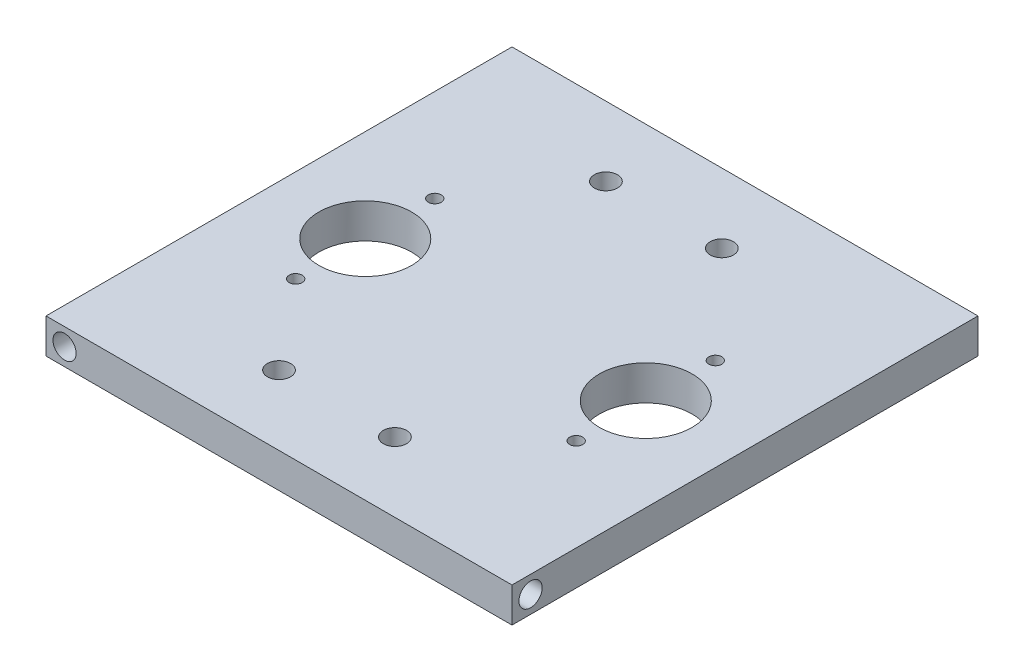
SolidWorks part; units mm, degrees
material "6061 Alloy"
ref_plane "Front" through (0, 0, 0) normal (0, 0, 1) x (1, 0, 0)
ref_plane "Top" through (0, 0, 0) normal (0, 1, 0) x (1, 0, 0)
ref_plane "Right" through (0, 0, 0) normal (1, 0, 0) x (0, 0, -1)
sketch "Sketch1" plane through (0, 0, 0) normal (0, 1, 0) x (1, 0, 0)
  line L1 (0, 0) -> (127.635, 0)
  line L2 (0, 0) -> (0, 127.635)
  line L3 (0, 127.635) -> (127.635, 127.635)
  line L4 (127.635, 0) -> (127.635, 127.635)
  dimension "D1" = 127.635
  dimension "D2" = 127.635
extrude "Main Plate" add sketch "Sketch1" along normal blind 9.525
sketch "Sketch2" plane through (0, 9.525, 0) normal (0, 1, 0) x (1, 0, 0)
  line L0 (0, 127.635) -> (0, 0) construction
  line L1 (127.635, 127.635) -> (0, 127.635) construction
  circle A0 centre (44.7675, 108.585) radius 3.175
  dimension "D1" = 6.35
  dimension "D2" = 44.7675
  dimension "D3" = 19.05
extrude "U-Bolt Hole" cut sketch "Sketch2" against normal blind 12.7
pattern_linear "U-Bolt Pattern" count 2 spacing 31.75 along (1, 0, 0) count 2 spacing 89.535 along (0, 0, 1) of "U-Bolt Hole"
sketch "Sketch3" plane through (0, 9.525, 0) normal (0, 1, 0) x (1, 0, 0)
  line L0 (0, 127.635) -> (0, 0) construction
  line L1 (0, 0) -> (127.635, 0) construction
  circle A0 centre (25.4, 42.9895) radius 1.778
  dimension "D1" = 3.556
  dimension "D2" = 25.4
  dimension "D3" = 42.9895
extrude "Raptor Bolt Hole" cut sketch "Sketch3" against normal blind 12.7
pattern_linear "Raptor Bolt Pattern" count 2 spacing 38.1 along (0, 0, -1) count 2 spacing 76.835 along (1, 0, 0) of "Raptor Bolt Hole"
sketch "Sketch4" plane through (0, 9.525, 0) normal (0, 1, 0) x (1, 0, 0)
  line L0 (0, 127.635) -> (0, 0) construction
  circle A0 centre (25.4, 62.0395) radius 12.7
  dimension "D1" = 25.4
  dimension "D2" = 19.05
  dimension "D3" = 25.4
extrude "Co2 Cylinder Hole" cut sketch "Sketch4" against normal blind 12.7
pattern_linear "Co2 Pattern" count 2 spacing 76.835 along (1, 0, 0) of "Co2 Cylinder Hole"
sketch "Sketch5" plane through (0, 0, 0) normal (0, 0, 1) x (1, 0, 0)
  line L0 (0, 9.525) -> (0, 0) construction
  line L1 (0, 0) -> (127.635, 0) construction
  circle A0 centre (5.08, 4.7625) radius 3.175
  dimension "D1" = 6.35
  dimension "D2" = 5.08
  dimension "D3" = 4.7625
extrude "Frame attachment hole 1" cut sketch "Sketch5" against normal blind 12.7
sketch "Sketch6" plane through (0, 0, 0) normal (-1, 0, 0) x (0, 0, 1)
  line L2 (-127.635, 0) -> (0, 0) construction
  line L3 (-127.635, 9.525) -> (-127.635, 0) construction
  circle A0 centre (-122.555, 4.7625) radius 3.175
  dimension "D1" = 6.35
  dimension "D2" = 4.7625
  dimension "D3" = 5.08
extrude "Frame attachment hole 2" cut sketch "Sketch6" against normal blind 12.7
sketch "Sketch7" plane through (0, 0, -127.635) normal (0, 0, -1) x (-1, 0, 0)
  line L2 (-127.635, 0) -> (0, 0) construction
  line L3 (-127.635, 9.525) -> (-127.635, 0) construction
  circle A0 centre (-122.555, 4.7625) radius 3.175
  dimension "D1" = 6.35
  dimension "D2" = 4.7625
  dimension "D3" = 5.08
extrude "Frame attachment hole 3" cut sketch "Sketch7" against normal blind 12.7
sketch "Sketch8" plane through (127.635, 0, 0) normal (1, 0, 0) x (0, 0, -1)
  line L2 (0, 0) -> (127.635, 0) construction
  line L3 (0, 9.525) -> (0, 0) construction
  circle A0 centre (5.08, 4.7625) radius 3.175
  dimension "D1" = 6.35
  dimension "D2" = 4.7625
  dimension "D3" = 5.08
extrude "Frame attachment hole 4" cut sketch "Sketch8" against normal blind 12.7
